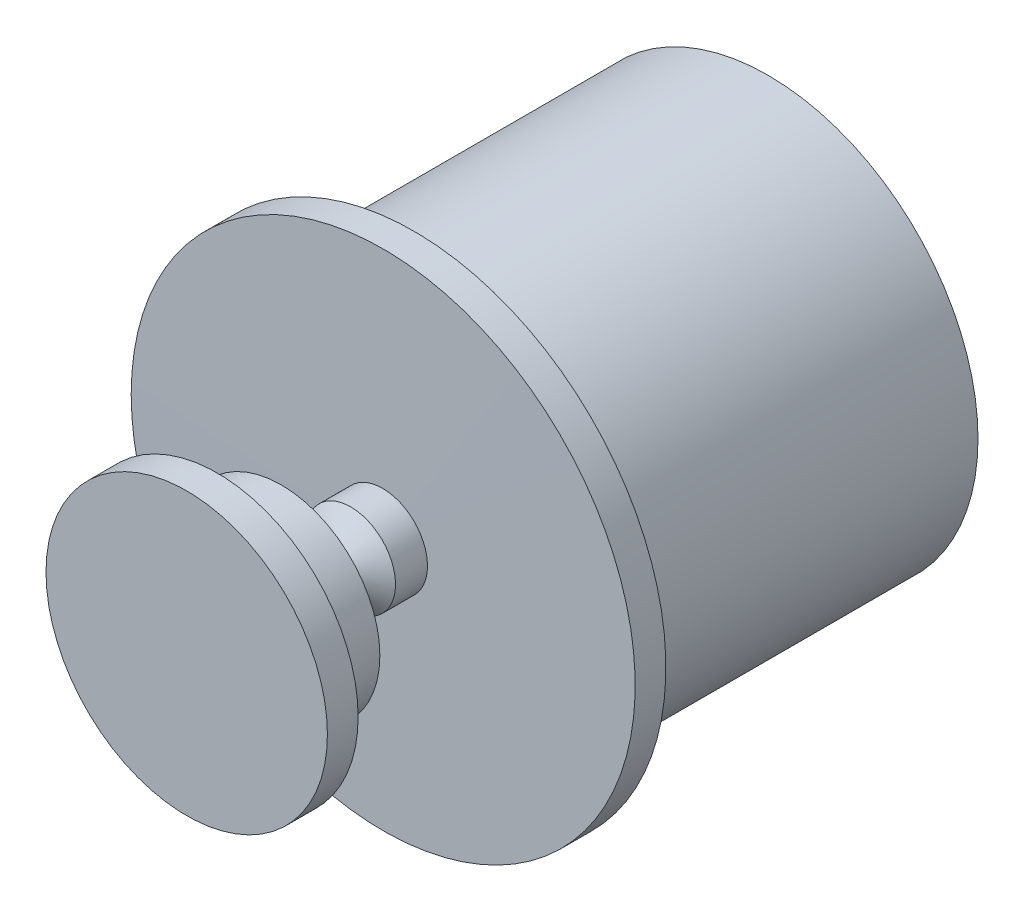
SolidWorks part; units mm, degrees
ref_plane "Front" through (0, 0, 0) normal (0, 0, 1) x (1, 0, 0)
ref_plane "Top" through (0, 0, 0) normal (0, 1, 0) x (1, 0, 0)
ref_plane "Right" through (0, 0, 0) normal (1, 0, 0) x (0, 0, -1)
sketch "Эскиз14" plane through (0, 0, 0) normal (0, 1, 0) x (1, 0, 0)
  line L0 (0, -600) -> (0, 0) construction
  line L1 (0, -441) -> (-110, -441)
  line L2 (-110, -441) -> (-110, -453)
  line L3 (-110, -453) -> (0, -453)
  line L4 (0, -441) -> (0, -453)
  dimension "D1" = 600
  dimension "D2" = 110
  dimension "D3" = 441
  dimension "D4" = 12
revolve "Повернуть11" add sketch "Эскиз14" angle 360 about L0
sketch "Эскиз15" plane through (0, 0, 0) normal (0, 1, 0) x (1, 0, 0)
  line L0 (0, 0) -> (0, -534.988) construction
  line L1 (-110, -441) -> (-110, -429)
  line L3 (-110, -441) -> (-75, -441)
  line L4 (110, -441) -> (-110, -441) construction
  line L5 (-75, -441) -> (-75, -381)
  line L6 (-75, -381) -> (-15, -381)
  line L7 (-15, -381) -> (-15, -379)
  line L8 (-110, -429) -> (-77, -429)
  line L9 (-15, -379) -> (-77, -379)
  line L10 (-77, -429) -> (-77, -379)
  dimension "D1" = 12
  dimension "D2" = 110
  dimension "D3" = 60
  dimension "D4" = 35
  dimension "D5" = 15
  dimension "D6" = 2
  dimension "D7" = 33
  dimension "D8" = 62
revolve "Повернуть12" add sketch "Эскиз15" angle 360 about L0
sketch "Эскиз16" plane through (0, 0, 0) normal (0, 1, 0) x (1, 0, 0)
  line L0 (0, 0) -> (0, -599.8085) construction
  line L1 (-15, -381) -> (-13, -381)
  line L4 (77, -379) -> (-77, -379) construction
  line L5 (-15, -381) -> (-15, -331)
  line L6 (-13, -381) -> (-13, -332.5)
  line L7 (-15, -331) -> (-13, -331)
  line L8 (-13, -332.5) -> (-11.5, -332.5)
  line L9 (-11.5, -332.5) -> (-11.5, -304.5)
  line L10 (-13, -331) -> (-13, -305.5)
  line L11 (-11.5, -304.5) -> (-18.2, -304.5)
  line L12 (-13, -305.5) -> (-15, -305.5)
  line L13 (-17.3, -307.5) -> (-15.7, -307.5)
  line L14 (-15.7, -307.5) -> (-15, -305.5)
  line L15 (-17.3, -307.5) -> (-18.2, -304.5)
  dimension "D1" = 2
  dimension "D2" = 13
  dimension "D3" = 2
  dimension "D4" = 50
  dimension "D5" = 1.5
  dimension "D6" = 1.5
  dimension "D7" = 28
  dimension "D8" = 27
  dimension "D9" = 6.7
  dimension "D10" = 2
  dimension "D11" = 2
  dimension "D12" = 4.3
  dimension "D13" = 1.6
revolve "Повернуть17" add sketch "Эскиз16" angle 360 about L0
sketch "Эскиз17" plane through (0, 0, 0) normal (0, 1, 0) x (1, 0, 0)
  line L0 (-15, -331) -> (-15, -379) construction
  line L1 (-15, -341) -> (-16.5, -341)
  line L2 (77, -379) -> (-77, -379) construction
  line L3 (-16.5, -341) -> (-16.5, -338)
  line L4 (-15, -341) -> (-15, -336.62)
  line L5 (-13, -323.4) -> (-33.5, -323.4)
  line L6 (15, -331) -> (-15, -331) construction
  line L7 (-13, -305.5) -> (-13, -331) construction
  line L8 (-15, -336.62) -> (-33.5, -323.4)
  line L9 (-16.5, -338) -> (-35, -324.78)
  line L10 (-33.5, -323.4) -> (-33.5, -283.4)
  line L11 (-35, -324.78) -> (-35, -299.78)
  line L12 (-33.5, -283.4) -> (-159.5, -283.4)
  line L13 (-159.5, -283.4) -> (-159.5, -287.4)
  line L14 (-159.5, -287.4) -> (-197, -287.4)
  line L15 (-197, -287.4) -> (-197, -299.4)
  line L16 (-197, -299.4) -> (-35, -299.78)
  line L17 (0, 0) -> (0, -530.5891) construction
  dimension "D7" = 40
  dimension "D1" = 38
  dimension "D2" = 1.5
  dimension "D3" = 3
  dimension "D4" = 4.38
  dimension "D5" = 7.6
  dimension "D6" = 20.5
  dimension "D8" = 25
  dimension "D9" = 126
  dimension "D10" = 4
  dimension "D11" = 37.5
  dimension "D12" = 12
revolve "Повернуть19" add sketch "Эскиз17" angle 360 about L17 region at (-108.3238, 0, 292.9284)
sketch "Эскиз18" plane through (0, 0, 0) normal (0, 1, 0) x (1, 0, 0)
  line L0 (-197, -287.4) -> (-197, -275.4)
  line L1 (-197, -287.4) -> (-170, -287.4)
  line L2 (197, -287.4) -> (-197, -287.4) construction
  line L3 (-170, -287.4) -> (-170, -282.4)
  line L4 (-170, -282.4) -> (-165, -282.4)
  line L5 (-165, -282.4) -> (-165, -287.4)
  line L6 (-165, -287.4) -> (-160, -287.4)
  line L7 (-160, -287.4) -> (-160, -6.4)
  line L8 (-197, -275.4) -> (-170, -275.4)
  line L9 (-170, -275.4) -> (-170, -277.4)
  line L10 (-170, -277.4) -> (-166, -277.4)
  line L11 (-166, -277.4) -> (-166, -275.4)
  line L12 (-166, -275.4) -> (-164, -275.4)
  line L13 (-164, -275.4) -> (-164, 1.6)
  line L14 (-164, 1.6) -> (-162, 1.6)
  line L15 (-162, 1.6) -> (-162, -6.4)
  line L16 (-162, -6.4) -> (-160, -6.4)
  line L17 (0, 0) -> (0, -519.2816) construction
  dimension "D1" = 12
  dimension "D2" = 27
  dimension "D3" = 5
  dimension "D4" = 5
  dimension "D5" = 5
  dimension "D6" = 281
  dimension "D7" = 27
  dimension "D8" = 2
  dimension "D9" = 4
  dimension "D10" = 2
  dimension "D11" = 277
  dimension "D12" = 2
  dimension "D13" = 8
revolve "Повернуть20" add sketch "Эскиз18" angle 360 about L17
sketch "Эскиз19" plane through (0, 0, 0) normal (0, 1, 0) x (1, 0, 0)
  line L0 (-162, 1.6) -> (-160, 1.6)
  line L1 (162, 1.6) -> (-162, 1.6) construction
  line L2 (-162, 1.6) -> (-162, -3.4)
  line L3 (-162, 1.6) -> (-162, -6.4) construction
  line L4 (-162, -3.4) -> (-154, -3.4)
  line L5 (-160, 1.6) -> (-160, -0.4)
  line L6 (-160, -0.4) -> (-157, -0.4)
  line L7 (-157, -0.4) -> (-157, 1.6)
  line L8 (-157, 1.6) -> (-64.5, 1.6)
  line L9 (-64.5, 1.6) -> (-64.5, -0.4)
  line L10 (-64.5, -0.4) -> (-61.5, -0.4)
  line L11 (-61.5, -0.4) -> (-61.5, 1.6)
  line L12 (-61.5, 1.6) -> (-59.5, 1.6)
  line L13 (-59.5, 1.6) -> (-59.5, -0.4)
  line L14 (-59.5, -0.4) -> (-56.5, -0.4)
  line L15 (-56.5, -0.4) -> (-56.5, 1.6)
  line L16 (164, 1.6) -> (-164, 1.6) construction
  line L17 (-56.5, 1.6) -> (-30.5, 1.6)
  line L18 (-150, -7.4) -> (-25.5, -7.4)
  line L19 (-154, -3.4) -> (-150, -7.4)
  line L20 (-25.5, -7.4) -> (-25.5, -6.4)
  line L21 (-25.5, -6.4) -> (-30.5, 1.6)
  line L22 (0, 0) -> (0, -521.8345) construction
  dimension "D1" = 2
  dimension "D2" = 5
  dimension "D3" = 8
  dimension "D4" = 2
  dimension "D5" = 3
  dimension "D6" = 92.5
  dimension "D7" = 2
  dimension "D8" = 3
  dimension "D9" = 2
  dimension "D10" = 2
  dimension "D11" = 3
  dimension "D12" = 26
  dimension "D13" = 9
  dimension "D14" = 12
  dimension "D15" = 124.5
  dimension "D16" = 1
revolve "Повернуть21" add sketch "Эскиз19" angle 360 about L22
sketch "Эскиз20" plane through (0, 0, 0) normal (0, 1, 0) x (1, 0, 0)
  line L0 (0, 0) -> (0, -558.111) construction
  line L1 (-156.5, -243.4) -> (-12.5, -243.4)
  line L2 (197, -275.4) -> (-197, -275.4) construction
  line L3 (-160, -6.4) -> (-160, -287.4) construction
  line L4 (-12.5, -243.4) -> (-12.5, -227.4)
  line L5 (-12.5, -227.4) -> (-14.5, -227.4)
  line L6 (-14.5, -227.4) -> (-14.5, -229.4)
  line L7 (-14.5, -229.4) -> (-16.5, -229.4)
  line L8 (-16.5, -229.4) -> (-16.5, -227.4)
  line L9 (-16.5, -227.4) -> (-119.5, -227.4)
  line L10 (-119.5, -227.4) -> (-119.5, -233.4)
  line L11 (-119.5, -233.4) -> (-130.5, -233.4)
  line L12 (-130.5, -233.4) -> (-130.5, -230.4)
  line L13 (-130.5, -230.4) -> (-136.5, -230.4)
  line L14 (-136.5, -230.4) -> (-136.5, -233.4)
  line L15 (-136.5, -233.4) -> (-156.5, -233.4)
  line L16 (-156.5, -233.4) -> (-156.5, -243.4)
  dimension "D1" = 32
  dimension "D2" = 3.5
  dimension "D3" = 144
  dimension "D4" = 16
  dimension "D5" = 2
  dimension "D6" = 2
  dimension "D7" = 2
  dimension "D8" = 2
  dimension "D9" = 103
  dimension "D10" = 6
  dimension "D11" = 11
  dimension "D12" = 3
  dimension "D13" = 6
  dimension "D14" = 20
  dimension "D15" = 3
revolve "Повернуть22" add sketch "Эскиз20" angle 360 about L0
sketch "Эскиз21" plane through (0, 0, 0) normal (0, 1, 0) x (1, 0, 0)
  line L0 (-16.5, -307.5) -> (-16.5, -301.5)
  line L1 (-17.3, -307.5) -> (17.3, -307.5) construction
  line L2 (-16.5, -301.5) -> (-19.5, -301.5)
  line L3 (-19.5, -301.5) -> (-19.5, -253.5)
  line L4 (-19.5, -253.5) -> (-16.5, -253.5)
  line L5 (-16.5, -253.5) -> (-16.5, -251)
  line L6 (-17, -301.5) -> (-18.479, -300.5)
  line L7 (-18.479, -300.5) -> (-17, -299.9062)
  line L8 (-17, -299.91) -> (-18.479, -298.91)
  line L9 (-18.479, -298.91) -> (-17, -298.3162)
  line L10 (-17, -298.32) -> (-18.479, -297.32)
  line L11 (-18.479, -297.32) -> (-17, -296.7262)
  line L12 (-17, -296.73) -> (-18.479, -295.73)
  line L13 (-18.479, -295.73) -> (-17, -295.1362)
  line L14 (-17, -295.14) -> (-18.479, -294.14)
  line L15 (-18.479, -294.14) -> (-17, -293.5462)
  line L16 (-17, -293.55) -> (-18.479, -292.55)
  line L17 (-18.479, -292.55) -> (-17, -291.9562)
  line L18 (-17, -291.96) -> (-18.479, -290.96)
  line L19 (-18.479, -290.96) -> (-17, -290.3662)
  line L20 (-17, -290.37) -> (-18.479, -289.37)
  line L21 (-18.479, -289.37) -> (-17, -288.7762)
  line L22 (-17, -288.78) -> (-18.479, -287.78)
  line L23 (-18.479, -287.78) -> (-17, -287.1862)
  line L24 (-17, -287.19) -> (-18.479, -286.19)
  line L25 (-18.479, -286.19) -> (-17, -285.5962)
  line L26 (-17, -285.6) -> (-18.479, -284.6)
  line L27 (-18.479, -284.6) -> (-17, -284.0062)
  line L28 (-17, -284.01) -> (-18.479, -283.01)
  line L29 (-18.479, -283.01) -> (-17, -282.4162)
  line L30 (-17, -282.42) -> (-18.479, -281.42)
  line L31 (-18.479, -281.42) -> (-17, -280.8262)
  line L32 (-17, -280.83) -> (-18.479, -279.83)
  line L33 (-18.479, -279.83) -> (-17, -279.2362)
  line L34 (-17, -279.24) -> (-18.479, -278.24)
  line L35 (-18.479, -278.24) -> (-17, -277.6462)
  line L36 (-17, -277.65) -> (-18.479, -276.65)
  line L37 (-18.479, -276.65) -> (-17, -276.0562)
  line L38 (-17, -276.06) -> (-18.479, -275.06)
  line L39 (-18.479, -275.06) -> (-17, -274.4662)
  line L40 (-17, -274.47) -> (-18.479, -273.47)
  line L41 (-18.479, -273.47) -> (-17, -272.8762)
  line L42 (-17, -272.88) -> (-18.479, -271.88)
  line L43 (-18.479, -271.88) -> (-17, -271.2862)
  line L44 (-17, -271.29) -> (-18.479, -270.29)
  line L45 (-18.479, -270.29) -> (-17, -269.6962)
  line L46 (-17, -269.7) -> (-18.479, -268.7)
  line L47 (-18.479, -268.7) -> (-17, -268.1062)
  line L48 (-17, -268.11) -> (-18.479, -267.11)
  line L49 (-18.479, -267.11) -> (-17, -266.5162)
  line L50 (-17, -266.52) -> (-18.479, -265.52)
  line L51 (-18.479, -265.52) -> (-17, -264.9262)
  line L52 (-17, -264.93) -> (-18.479, -263.93)
  line L53 (-18.479, -263.93) -> (-17, -263.3362)
  line L54 (-17, -263.34) -> (-18.479, -262.34)
  line L55 (-18.479, -262.34) -> (-17, -261.7462)
  line L56 (-17, -261.75) -> (-18.479, -260.75)
  line L57 (-18.479, -260.75) -> (-17, -260.1562)
  line L58 (-17, -260.16) -> (-18.479, -259.16)
  line L59 (-18.479, -259.16) -> (-17, -258.5662)
  line L60 (-17, -258.57) -> (-18.479, -257.57)
  line L61 (-18.479, -257.57) -> (-17, -256.9762)
  line L62 (-17, -256.98) -> (-18.479, -255.98)
  line L63 (-18.479, -255.98) -> (-17, -255.3862)
  line L64 (-17, -255.39) -> (-18.479, -254.39)
  line L65 (-18.479, -254.39) -> (-17, -253.7962)
  line L66 (-17, -253.7962) -> (-17, -253.5)
  line L67 (-18.2, -251) -> (-10.2, -251)
  line L68 (-16.5, -251) -> (-16.5, -247.5)
  line L69 (-10.2, -251) -> (-10.2, -227.4)
  line L70 (119.5, -227.4) -> (-119.5, -227.4) construction
  line L71 (-10.2, -227.4) -> (-12.5, -227.4)
  line L72 (12.5, -227.4) -> (-12.5, -227.4) construction
  line L73 (-12.5, -227.4) -> (-12.5, -250)
  line L74 (-12.5, -250) -> (-15.03, -250)
  line L75 (-16.5, -247.5) -> (-17.3, -247.5)
  line L76 (-16.5, -247.5) -> (-15.7, -247.5)
  line L77 (-17.3, -247.5) -> (-18.2, -251)
  line L78 (-15.7, -247.5) -> (-15.03, -250)
  line L79 (0, 0) -> (0, -502.5003) construction
  dimension "D1" = 0.8
  dimension "D2" = 8
  dimension "D3" = 1.7
  dimension "D4" = 48
  dimension "D5" = 3
  dimension "D6" = 2.5
  dimension "D7" = 1
  dimension "D8" = 2.5
  dimension "D9" = 1.5938
  dimension "D11" = 3.5
  dimension "D12" = 1
  dimension "D13" = 2.53
  dimension "D14" = 0.8
  dimension "D15" = 0.8
  dimension "D10" = 30
revolve "Повернуть26" add sketch "Эскиз21" angle 360 about L79 region at (-18.5662, 0, 277.4664)
sketch "Эскиз22" plane through (0, 0, 0) normal (0, 1, 0) x (1, 0, 0)
  line L0 (-156.5, -232.4) -> (-136.5, -232.4)
  line L1 (156.5, -233.4) -> (-156.5, -233.4) construction
  line L2 (-136.5, -230.4) -> (-136.5, -233.4) construction
  line L3 (-156.5, -232.4) -> (-156.5, -216.4)
  line L4 (-156.5, -216.4) -> (-123.5, -216.4)
  line L5 (-123.5, -216.4) -> (-123.5, -19.4)
  line L6 (-123.5, -19.4) -> (-121.75, -19.4)
  line L7 (-121.75, -19.4) -> (-121.75, -20.9)
  line L8 (-121.75, -20.9) -> (-120.5, -20.9)
  line L9 (-120.5, -20.9) -> (-120.5, -229.4)
  dimension "D1" = 1
  dimension "D2" = 16
  dimension "D3" = 33
  dimension "D4" = 197
  dimension "D5" = 1.75
  dimension "D6" = 1.5
  dimension "D7" = 1.25
  dimension "D8" = 208.5
